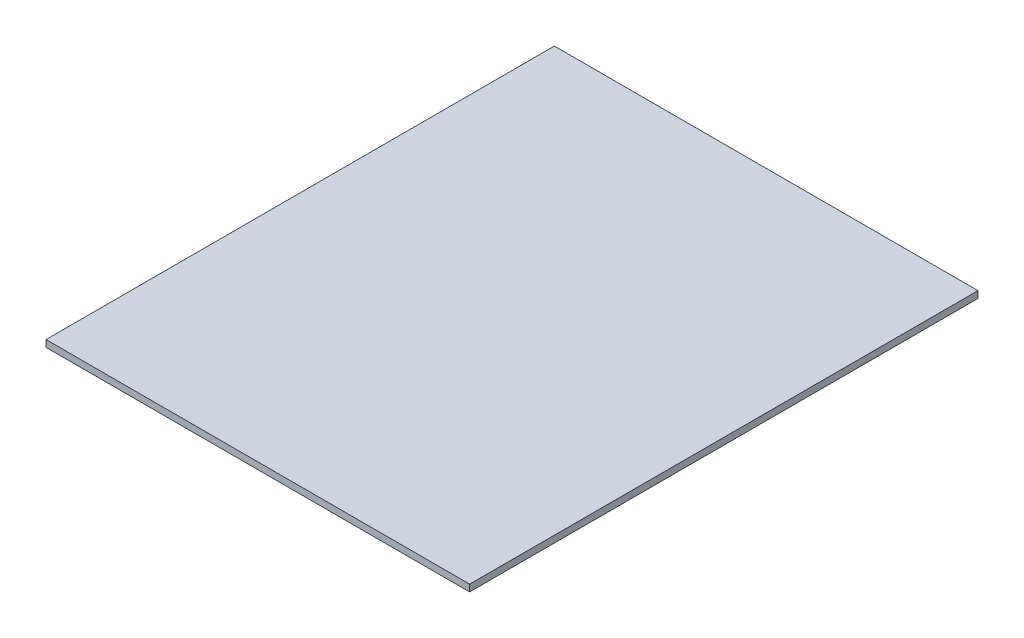
SolidWorks part; units mm, degrees
ref_plane "Front Plane" through (0, 0, 0) normal (0, 0, 1) x (1, 0, 0)
ref_plane "Top Plane" through (0, 0, 0) normal (0, 1, 0) x (1, 0, 0)
ref_plane "Right Plane" through (0, 0, 0) normal (1, 0, 0) x (0, 0, -1)
sketch "Sketch1" plane through (0, 0, 0) normal (0, 1, 0) x (1, 0, 0)
  line L1 (50, -60) -> (-50, -60)
  line L2 (50, -60) -> (50, 60)
  line L3 (50, 60) -> (-50, 60)
  line L4 (-50, -60) -> (-50, 60)
  line L5 (50, -60) -> (-50, 60) construction
  line L6 (50, 60) -> (-50, -60) construction
  point P0 (0, 0)
  dimension "D1" = 100
  dimension "D2" = 120
extrude "Boss-Extrude1" add sketch "Sketch1" along normal blind 1.6
